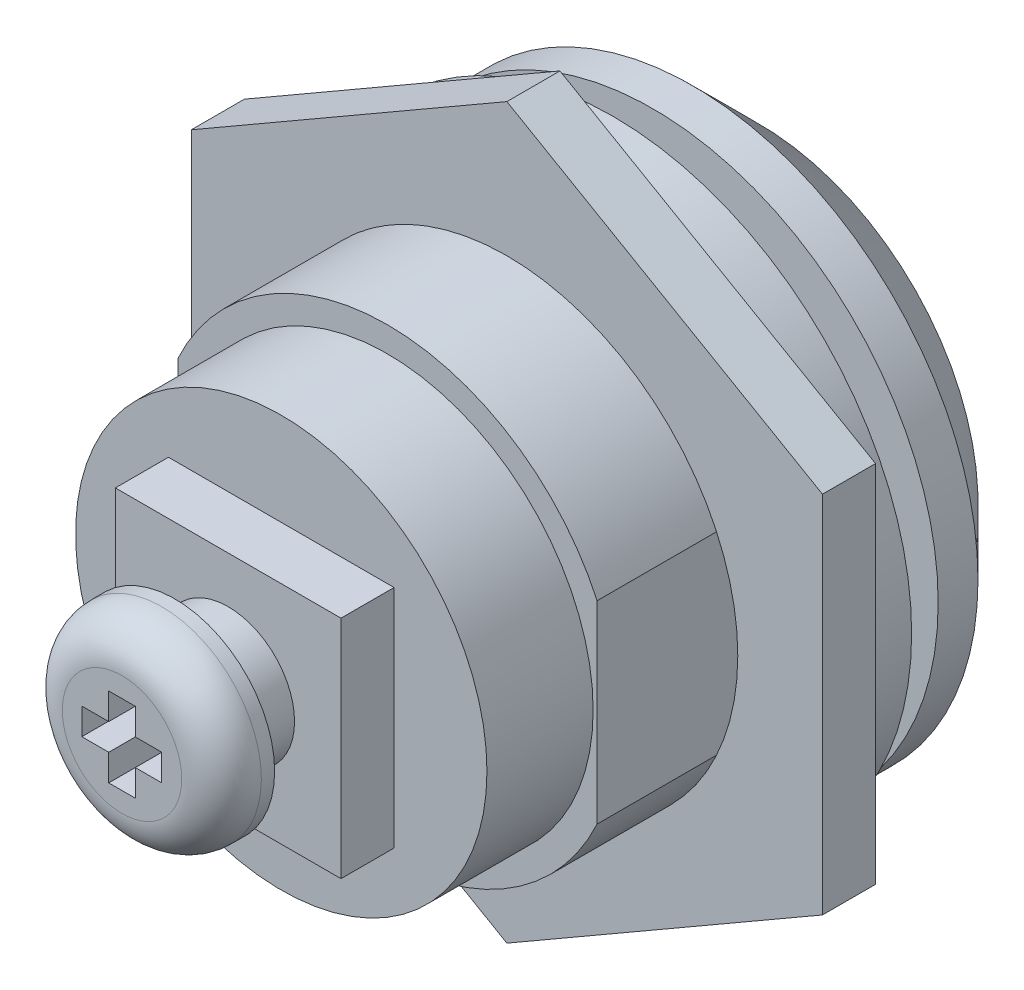
SolidWorks part; units mm, degrees
ref_plane "前视基准面" through (0, 0, 0) normal (0, 0, 1) x (1, 0, 0)
ref_plane "上视基准面" through (0, 0, 0) normal (0, 1, 0) x (1, 0, 0)
ref_plane "右视基准面" through (0, 0, 0) normal (1, 0, 0) x (0, 0, -1)
sketch "草图1" plane through (0, 0, 0) normal (0, 0, 1) x (1, 0, 0)
  line L0 (7.9, 3.6442) -> (7.9, -3.6442)
  line L1 (-7.9, 3.6442) -> (-7.9, -3.6442)
  line L2 (-15.0917, 0) -> (11.0145, 0) construction
  line L3 (0, 12.1407) -> (0, -11.873) construction
  arc A0 (-7.9, -3.6442) -> (7.9, -3.6442) centre (0, 0) ccw
  arc A1 (7.9, 3.6442) -> (-7.9, 3.6442) centre (0, 0) ccw
  dimension "D1" = 8.7
  dimension "D2" = 15.8
extrude "拉伸1" add sketch "草图1" along normal blind 14
sketch "草图3" plane through (0, 0, 0) normal (0, 0, -1) x (-1, 0, 0)
  circle A2 centre (0, 0) radius 10.75
  dimension "D1" = 21.5
extrude "拉伸2" add sketch "草图3" along normal blind 4
chamfer "倒角1" distance 2.5 angle 45 1 edges at (-10.75, 0, -4)
ref_plane "基准面2" through (0, 0, 1.5) normal (0, 0, 1) x (1, 0, 0)
sketch "草图4" plane through (0, 0, 1.5) normal (0, 0, 1) x (1, 0, 0)
  line L4 (-7.1166, 3.7625) -> (-7.1166, -3.7625)
  line L5 (7.1166, -3.7625) -> (7.1166, 3.7625)
  arc A1 (-7.1166, -3.7625) -> (7.1166, -3.7625) centre (0, 0) ccw
  arc A2 (7.1166, 3.7625) -> (-7.1166, 3.7625) centre (0, 0) ccw
  circle A6 centre (0, 0) radius 11.25
  circle A7 centre (0, 0) radius 11.25
  dimension "D1" = 0.5
extrude "拉伸3" add sketch "草图4" along normal blind 2
sketch "草图5" plane through (0, 0, 14) normal (0, 0, 1) x (1, 0, 0)
  line L0 (-14.5235, 0) -> (14.0386, 0) construction
  line L1 (0, 12.5838) -> (0, -12.2929) construction
  line L3 (-4.25, 4.25) -> (4.25, 4.25)
  line L4 (-4.25, 4.25) -> (-4.25, -4.25)
  line L5 (-4.25, -4.25) -> (4.25, -4.25)
  line L6 (4.25, 4.25) -> (4.25, -4.25)
  dimension "D1" = 8.5
  dimension "D2" = 8.5
extrude "拉伸4" add sketch "草图5" along normal blind 2
sketch "草图6" plane through (0, 0, 16) normal (0, 0, 1) x (1, 0, 0)
  line L0 (-9.4803, 0) -> (11.25, 0) construction
  line L1 (0, 7.3466) -> (0, -7.2011) construction
  circle A0 centre (0, 0) radius 11.25 construction
  circle A1 centre (0, 0) radius 2.5
  dimension "D1" = 5
extrude "拉伸5" add sketch "草图6" along normal blind 2
ref_plane "基准面1" through (0, 0, 4.7) normal (0, 0, 1) x (1, 0, 0)
sketch "草图7" plane through (0, 0, 18) normal (0, 0, 1) x (1, 0, 0)
  circle A0 centre (0, 0) radius 3.75
  dimension "D1" = 7.5
extrude "拉伸6" add sketch "草图7" along normal blind 2
fillet "圆角1" radius 1.5 1 edges at (3.75, 0, 20)
sketch "草图8" plane through (0, 0, 20) normal (0, 0, 1) x (1, 0, 0)
  line L0 (-2.7105, 0) -> (2.6865, 0) construction
  line L1 (-1.5147, 0.5) -> (-0.5, 0.5)
  line L2 (-1.5147, 0.5) -> (-1.5147, -0.5)
  line L3 (-1.5147, -0.5) -> (-0.5, -0.5)
  line L4 (1.4853, 0.5) -> (1.4853, -0.5)
  line L5 (-0.5, 1.5) -> (0.5, 1.5)
  line L6 (-0.5, 1.5) -> (-0.5, 0.5)
  line L7 (-0.5, -1.5) -> (0.5, -1.5)
  line L8 (0.5, 1.5) -> (0.5, 0.5)
  line L9 (0, 3.1568) -> (0, -3.2539) construction
  line L10 (0.5, -0.5) -> (0.5, -1.5)
  line L11 (0.5, 0.5) -> (1.4853, 0.5)
  line L12 (-0.5, -0.5) -> (-0.5, -1.5)
  line L13 (0.5, -0.5) -> (1.4853, -0.5)
  dimension "D1" = 1
  dimension "D2" = 1
  dimension "D3" = 3
  dimension "D4" = 3
extrude "切除-拉伸1" cut sketch "草图8" against normal blind 2
sketch "草图9" plane through (0, 0, 3.5) normal (0, 0, 1) x (1, 0, 0)
  line L0 (-23.5872, 0) -> (22.3691, 0) construction
  line L5 (0, 23.4548) -> (0, -20.323) construction
  line L8 (11.8901, -6.8648) -> (0, -13.7295)
  line L9 (-11.8901, -6.8648) -> (-11.8901, 6.8648)
  line L10 (0, 13.7295) -> (11.8901, 6.8648)
  line L11 (11.8901, 6.8648) -> (11.8901, -6.8648)
  line L12 (-11.8901, 6.8648) -> (0, 13.7295)
  line L13 (0, -13.7295) -> (-11.8901, -6.8648)
  circle A3 centre (0, 0) radius 8.7
  dimension "D1" = 17.4
extrude "拉伸7" add sketch "草图9" along normal blind 2
sketch "草图12" plane through (0, 0, -4) normal (0, 0, -1) x (-1, 0, 0)
  circle A0 centre (0, 0) radius 7.25
  dimension "D1" = 14.5
extrude "拉伸8" add sketch "草图12" along normal blind 0.2
fillet "圆角2" radius 0.2 1 edges at (-7.25, 0, -4.2)
sketch "草图10" plane through (0, 0, -4.2) normal (0, 0, -1) x (-1, 0, 0)
  line L0 (0, 8.25) -> (0, -6.9624) construction
  line L1 (-0.9, 3.5) -> (-0.9, -3.5)
  line L2 (0, -3.5) -> (0, -0.7)
  line L3 (0, -0.7) -> (0.9, -0.7)
  line L4 (0.9, -0.7) -> (0.9, 3.5)
  line L5 (0.9, 3.5) -> (-0.9, 3.5)
  line L6 (-0.9, -3.5) -> (0, -3.5)
  line L7 (-5.4732, 0) -> (3.9571, 0) construction
  circle A1 centre (0, 0) radius 8.25 construction
  dimension "D1" = 1.8
  dimension "D2" = 7
  dimension "D3" = 4.2
extrude "切除-拉伸2" cut sketch "草图10" against normal up to surface (18.2 mm away) up to face at (0, 0, 14)
sketch "草图13" plane through (0, 0, 14) normal (0, 0, 1) x (1, 0, 0)
  line L4 (7.9, -3.6442) -> (7.9, 3.6442)
  line L5 (-7.9, 3.6442) -> (-7.9, -3.6442)
  line L6 (7.9, -3.6442) -> (7.9, 3.6442)
  line L7 (-7.9, 3.6442) -> (-7.9, -3.6442)
  circle A2 centre (0, 0) radius 7.75
  arc A4 (-7.9, -3.6442) -> (7.9, -3.6442) centre (0, 0) ccw
  arc A5 (7.9, 3.6442) -> (-7.9, 3.6442) centre (0, 0) ccw
  arc A6 (-7.9, -3.6442) -> (7.9, -3.6442) centre (0, 0) ccw
  arc A7 (7.9, 3.6442) -> (-7.9, 3.6442) centre (0, 0) ccw
  dimension "D2" = 15.5
  dimension "D1" = 0
extrude "切除-拉伸3" cut sketch "草图13" against normal blind 4
